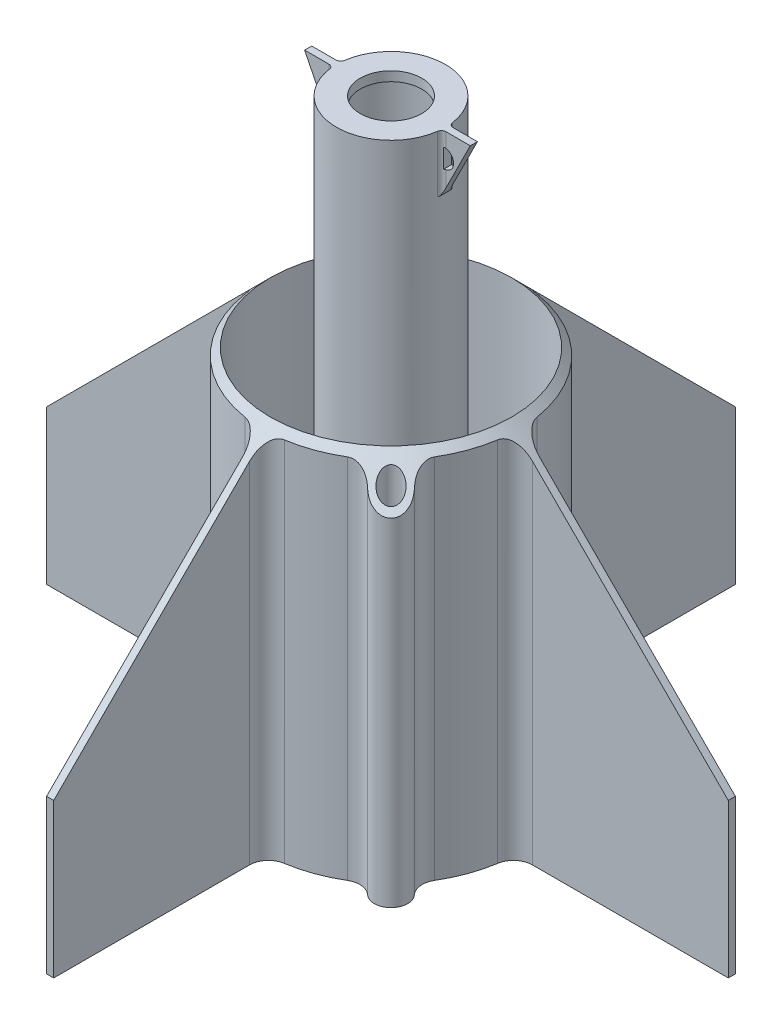
SolidWorks part; units mm, degrees
ref_plane "Front Plane" through (0, 0, 0) normal (0, 0, 1) x (1, 0, 0)
ref_plane "Top Plane" through (0, 0, 0) normal (0, 1, 0) x (1, 0, 0)
ref_plane "Right Plane" through (0, 0, 0) normal (1, 0, 0) x (0, 0, -1)
sketch "Sketch1" plane through (0, 0, 0) normal (0, 0, 1) x (1, 0, 0)
  line L0 (6.5, 125) -> (11.5, 125)
  line L1 (11.5, 125) -> (11.5, 2)
  line L2 (11.5, 2) -> (25.5, 2)
  line L3 (25.5, 2) -> (25.5, 80)
  line L4 (25.5, 80) -> (27, 80)
  line L5 (27, 80) -> (27, 0)
  line L6 (27, 0) -> (10.35, 0)
  line L7 (10.35, 0) -> (10.35, 123)
  line L8 (10.35, 123) -> (6.5, 123)
  line L9 (6.5, 123) -> (6.5, 125)
  line L10 (0, -54.45) -> (0, 54.45) construction
  line L11 (-6.5, 123) -> (-6.5, 125) construction
  line L12 (-10.35, 123) -> (-6.5, 123) construction
  line L13 (-10.35, 0) -> (-10.35, 123) construction
  line L14 (-27, 0) -> (-10.35, 0) construction
  line L15 (-27, 80) -> (-27, 0) construction
  line L16 (-25.5, 80) -> (-27, 80) construction
  line L17 (-25.5, 2) -> (-25.5, 80) construction
  line L18 (-11.5, 2) -> (-25.5, 2) construction
  line L19 (-11.5, 125) -> (-11.5, 2) construction
  line L20 (-6.5, 125) -> (-11.5, 125) construction
  line L21 (0, 0) -> (0, 125) construction
  dimension "D1" = 2
  dimension "D2" = 2
  dimension "D3" = 80
  dimension "D4" = 125
  dimension "D5" = 20.7
  dimension "D6" = 23
  dimension "D7" = 13
  dimension "D8" = 51
  dimension "D9" = 54
revolve "Revolve2" add sketch "Sketch1" angle 360 about L21
sketch "Sketch3" plane through (0, 0, 0) normal (1, 0, 0) x (0, 0, -1)
  line L0 (-27, 80) -> (-27, 0) construction
  line L1 (-26, 80) -> (-26, 0) construction
  line L2 (25.5, 80) -> (-25.5, 80) construction
  line L3 (-27, 80) -> (-72, 80)
  line L4 (27, 80) -> (-27, 80) construction
  line L5 (-72, 80) -> (-72, 0)
  line L6 (-72, 0) -> (-26, 0)
  line L7 (-27, 80) -> (-26, 80)
  line L8 (-26, 80) -> (-26, 0)
  dimension "D1" = 1
  dimension "D3" = 45
extrude "Boss-Extrude1" add sketch "Sketch3" along normal mid plane 1.5
pattern_circular "CirPattern1" count 4 over 360 about axis through (0, 0, 0) along (0, -1, 0) of "Boss-Extrude1"
sketch "Sketch4" plane through (0, 0, 0) normal (0, 0, 1) x (1, 0, 0)
  line L0 (11.5, 125) -> (11.5, 80) construction
  line L1 (26.9896, 80) -> (0.75, 80) construction
  line L2 (11.5, 2) -> (11.5, 125) construction
  line L3 (10.5, 125) -> (10.5, 80) construction
  line L4 (11.5, 125) -> (-11.5, 125) construction
  line L5 (11.5, 125) -> (17.5, 125)
  line L6 (17.5, 125) -> (11.5, 113)
  line L7 (11.5, 113) -> (10.5, 113)
  line L8 (10.5, 113) -> (10.5, 125)
  line L9 (10.5, 125) -> (11.5, 125)
  dimension "D1" = 1
  dimension "D2" = 6
  dimension "D3" = 12
extrude "Boss-Extrude2" add sketch "Sketch4" along normal mid plane 1.5
sketch "Sketch5" plane through (0, 0, 0.75) normal (0, 0, 1) x (1, 0, 0)
  line L0 (11.9755, 125) -> (11.9755, 113.951) construction
  line L1 (17.5, 125) -> (11.4755, 125) construction
  line L2 (11.5, 113) -> (17.5, 125) construction
  line L3 (11.4755, 125) -> (11.4755, 113) construction
  line L4 (11.9755, 122) -> (11.9755, 118)
  arc A0 (11.9755, 122) -> (11.9755, 118) centre (11.9755, 120) cw
  dimension "D2" = 180
  dimension "D3" = 2
  dimension "D1" = 0.5
  dimension "D4" = 3
extrude "Cut-Extrude2" cut sketch "Sketch5" against normal through all both and the other way through all
mirror "Mirror1" about plane through (0, 0, 0) normal (1, 0, 0) of "Cut-Extrude2", "Boss-Extrude2"
sketch "Sketch7" plane through (0, 0, 0) normal (0, 1, 0) x (1, 0, 0)
  line L0 (0, 0) -> (30.7111, 30.7111) construction
  line L1 (0, 0) -> (72.9642, 0) construction
  dimension "D1" = 45
ref_plane "Plane_direction_guidance" through (0, 0, 0) normal (0.7071, 0, 0.7071) x (0.7071, 0, -0.7071)
sketch "Sketch8" plane through (0, 0, 0) normal (0, 1, 0) x (1, 0, 0)
  line L0 (0, 0) -> (35.9359, -35.9359) construction
  line L1 (72, -0.75) -> (26.9896, -0.75) construction
  line L2 (1.744, -36.4398) -> (38.2738, 0.09) construction
  line L3 (-5.3582, -42.1278) -> (40.669, 3.8995) construction
  line L4 (15.9099, -20.8597) -> (18.5616, -23.5113)
  line L5 (15.9099, -20.8597) -> (20.8597, -15.9099)
  line L6 (23.5113, -18.5616) -> (20.8597, -15.9099)
  line L7 (18.5616, -23.5113) -> (23.5113, -18.5616) construction
  line L8 (15.7896, -23.1013) -> (23.8905, -15.0004) construction
  arc A0 (0.75, -26.9896) -> (26.9896, -0.75) centre (0, 0) ccw construction
  arc A1 (18.5616, -23.5113) -> (23.5113, -18.5616) centre (21.0364, -21.0364) ccw
  circle A2 centre (21.0364, -21.0364) radius 2.25 construction
  point P14 (18.3848, -18.3848)
  dimension "D3" = 180
  dimension "D4" = 7
  dimension "D5" = 4.5
  dimension "D1" = 45
  dimension "D2" = 1
  dimension "D6" = 0.5
extrude "Boss-Extrude3" add sketch "Sketch8" along normal up to surface (80 mm away)
sketch "Sketch9" plane through (0, 0, 0) normal (0, -1, 0) x (1, 0, 0)
  circle A0 centre (21.0364, 21.0364) radius 2.25
  dimension "D1" = 4.5
extrude "Cut-Extrude3" cut sketch "Sketch9" against normal through all both and the other way through all
mirror "Mirror2" about plane through (0, 0, 0) normal (0.7071, 0, 0.7071) of "Boss-Extrude3", "Cut-Extrude3"
sketch "Sketch10" plane through (0, 0, 0) normal (0, 0, 1) x (1, 0, 0)
  line L0 (24.9896, 98.8616) -> (24.9896, -7.2473) construction
  line L1 (77, 98.8616) -> (77, -16.5651) construction
  line L2 (72, 80) -> (72, 0) construction
  line L3 (26.9896, 80) -> (26.9896, 0) construction
  line L4 (24.9896, 85) -> (77, 85)
  line L5 (77, 85) -> (77, 27.4896)
  line L6 (77, 27.4896) -> (24.9896, 79.5)
  line L7 (24.9896, 79.5) -> (24.9896, 85)
  line L8 (26.9896, 80) -> (72, 80) construction
  line L9 (26.9896, 80) -> (21.4057, 80) construction
  line L10 (0, 125) -> (0, 0) construction
  line L11 (11.4755, 125) -> (-11.4755, 125) construction
  dimension "D1" = 5
  dimension "D2" = 2
  dimension "D3" = 5
  dimension "D4" = 0.5
  dimension "D5" = 45
revolve "Cut-Revolve1" cut sketch "Sketch10" angle 360 about L10
fillet "Fillet2" radius 4 12 edges at (-0.75, 38.7448, 26.9896) (0.75, 38.7448, 26.9896) (26.9896, 38.7448, 0.75) (0.75, 38.7448, -26.9896) (-26.9896, 38.7448, 0.75) (-26.9896, 38.7448, -0.75) (-0.75, 38.7448, -26.9896) (-16.4559, 38.7448, -21.4057) (26.9896, 38.7448, -0.75) (16.4559, 38.7448, 21.4057) (21.4057, 38.7448, 16.4559) (-21.4057, 38.7448, -16.4559)
fillet "Fillet3" radius 6 1 edges at (0, 2, -25.5)
fillet "Fillet4" radius 6 1 edges at (0, 2, -11.5)
fillet "Fillet8" radius 1 4 edges at (11.4755, 119, 0.75) (11.4755, 119, -0.75) (-11.4755, 119, 0.75) (-11.4755, 119, -0.75)
